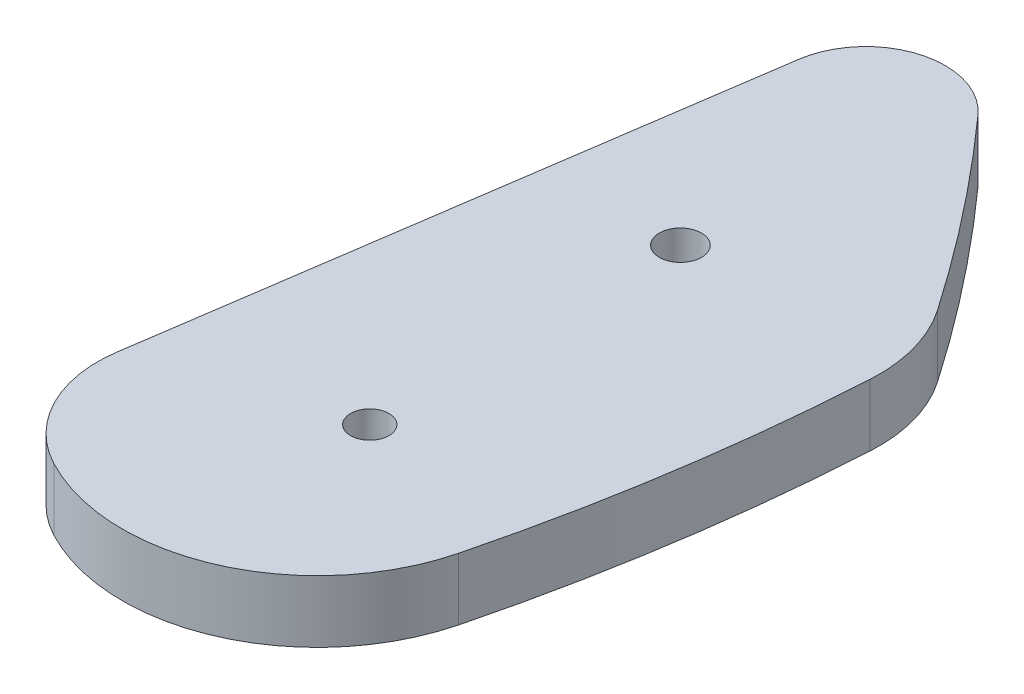
SolidWorks part; units mm, degrees
ref_plane "Front Plane" through (0, 0, 0) normal (0, 0, 1) x (1, 0, 0)
ref_plane "Top Plane" through (0, 0, 0) normal (0, 1, 0) x (1, 0, 0)
ref_plane "Right Plane" through (0, 0, 0) normal (1, 0, 0) x (0, 0, -1)
sketch "Sketch1" plane through (0, 0, 0) normal (0, 1, 0) x (1, 0, 0)
  line L44 (-43.1946, 148.7152) -> (-50.2252, 100.8707)
  arc A149 (-22.4566, 100.5997) -> (-18.0206, 129.2968) centre (-171.2572, 138.2924) ccw
  arc A150 (-18.0206, 129.2968) -> (-20.1164, 136.8055) centre (-30, 130) ccw
  arc A151 (-20.1164, 136.8055) -> (-32.0981, 152.0476) centre (-146.5445, 49.7519) ccw
  arc A152 (-32.0981, 152.0476) -> (-43.1946, 148.7152) centre (-36.8667, 147.7853) ccw
  arc A158 (-22.4566, 100.5997) -> (-45.0004, 90.5736) centre (-37.6721, 104.4539) cw
  arc A159 (-50.2252, 100.8707) -> (-45.0004, 90.5736) centre (-40.3315, 99.4168) ccw
  circle A160 centre (-35, 131) radius 1.7
  circle A161 centre (-35, 106) radius 1.5461
  dimension "D3" = 12
  dimension "D1" = 10
extrude "Boss-Extrude2" add sketch "Sketch1" along normal blind 5
